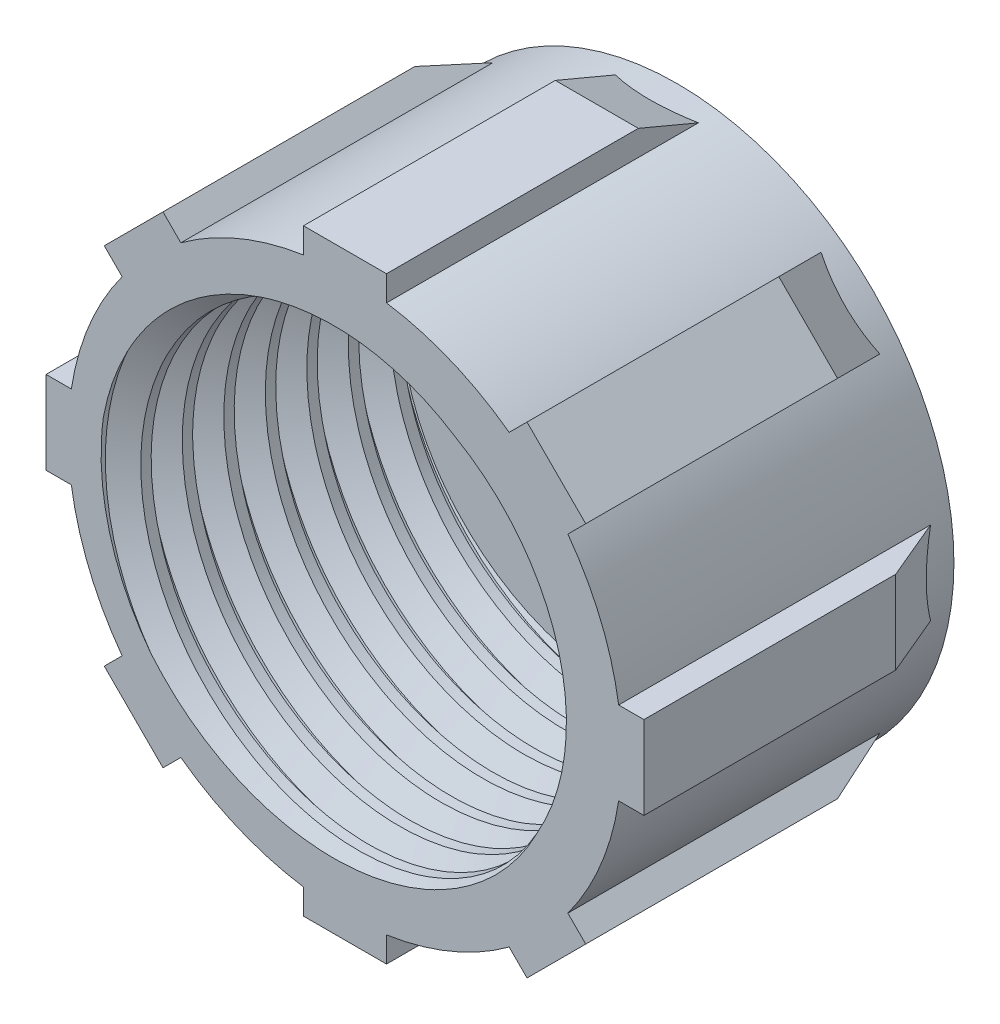
SolidWorks part; units mm, degrees
ref_plane "Front Plane" through (0, 0, 0) normal (0, 0, 1) x (1, 0, 0)
ref_plane "Top Plane" through (0, 0, 0) normal (0, 1, 0) x (1, 0, 0)
ref_plane "Right Plane" through (0, 0, 0) normal (1, 0, 0) x (0, 0, -1)
sketch "Sketch1" plane through (0, 0, 0) normal (0, 0, 1) x (1, 0, 0)
  circle A0 centre (0, 0) radius 10
  dimension "D1" = 20
extrude "Boss-Extrude1" add sketch "Sketch1" along normal blind 12
sketch "Sketch2" plane through (0, 0, 12) normal (0, 0, 1) x (1, 0, 0)
  circle A0 centre (0, 0) radius 8
  dimension "D1" = 16
extrude "Cut-Extrude1" cut sketch "Sketch2" against normal blind 10
thread "Thread1" pitch 1.5 method cut profile "Thread Profile1" start angle 0, offset 5, length 0, pitch 1.5, diameter 16
ref_plane "Plane1" through (-8, 0, 17) normal (0, -1, 0) x (-1, 0, 0)
sketch "Thread Profile1" plane through (-8, 0, 17) normal (0, -1, 0) x (-1, 0, 0)
  line L0 (0, 0) -> (0, 1.5) construction
  line L1 (0, 0) -> (0.8119, 0.4687)
  line L2 (0.8119, 0.4687) -> (0.8119, 0.6562)
  line L3 (0.8119, 0.6562) -> (0, 1.125)
  line L4 (0.8119, 0.5625) -> (0, 0.5625) construction
  line L11 (0, 0) -> (0, 1.125)
  point P2 (0, 0)
  dimension "Pitch" = 1.5
  dimension "Profile_Angle" = 60
  dimension "Profile_Land" = 0.1875
  dimension "Profile_Height" = 0.8119
sketch "Sketch6" plane through (0, 0, 0) normal (1, 0, 0) x (0, 0, -1)
  line L0 (0, 10) -> (-12, 10) construction
  line L1 (-1, 10) -> (-12, 10)
  line L2 (-1, 10) -> (-2.9026, 10.8)
  line L3 (-2.9026, 10.8) -> (-12, 10.8)
  line L4 (-12, 10.8) -> (-12, 10)
  line L5 (-1, 10) -> (-0.1388, 9.6379)
  line L6 (-0.1388, 9.6379) -> (-12, 9.6379)
  line L7 (-12, 10) -> (-12, -10) construction
  line L8 (-12, 9.6379) -> (-12, 10)
  dimension "D1" = 11
  dimension "D2" = 0.8
  dimension "D3" = 0.3621
extrude "Boss-Extrude2" add sketch "Sketch6" along normal blind 1.5 and the other way blind 1.5 contours L3 L4 L1 L2 | L8 L6 L5 L1 region at (0, 9.8167, 6.282) region at (0, 10.3874, 6.9606)
pattern_circular "CirPattern1" count 8 over 360 about axis through (0, 0, 12) along (0, 0, -1) of "Boss-Extrude2" reverse direction yes
